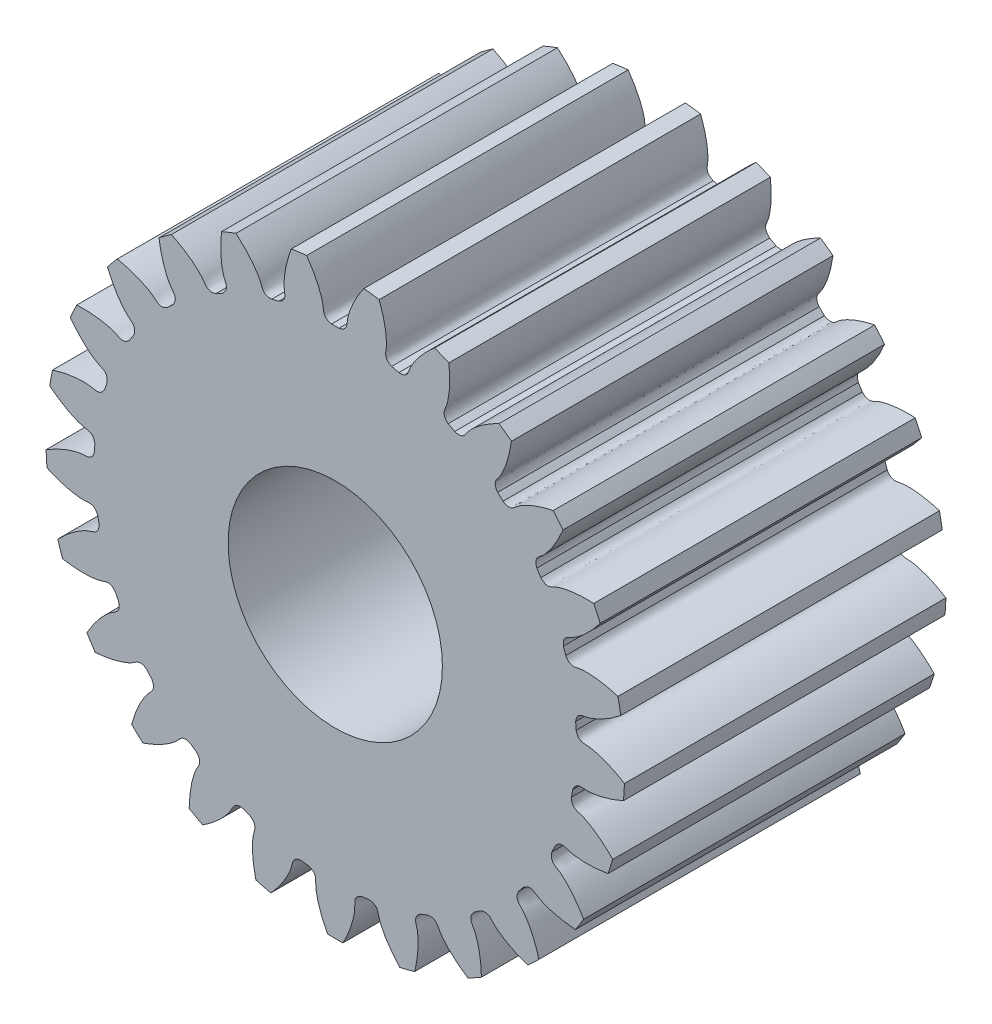
SolidWorks part; units mm, degrees
ref_plane "前视基准面" through (0, 0, 0) normal (0, 0, 1) x (1, 0, 0)
ref_plane "上视基准面" through (0, 0, 0) normal (0, 1, 0) x (1, 0, 0)
ref_plane "右视基准面" through (0, 0, 0) normal (1, 0, 0) x (0, 0, -1)
sketch "草图1" plane through (0, 0, 0) normal (0, 0, 1) x (1, 0, 0)
  circle A0 centre (0, 0) radius 2.7
extrude "凸台-拉伸1" add sketch "草图1" along normal blind 3
ref_axis "基准轴1" through (0, 0, 3) along (0, 0, -1)
sketch "草图2" plane through (0, 0, 0) normal (0, 0, 1) x (1, 0, 0)
  line L0 (0, 0) -> (0, 2.7) construction
  circle A0 centre (0, 0) radius 2.7 construction
  arc A1 (0.0344, 2.2497) -> (-0.0344, 2.2497) centre (0, 0) ccw
  arc A2 (0.6411, 3.063) -> (-0.6411, 3.063) centre (0, 0) ccw
  spline S0 degree 3 poles (0.0344, 2.2497) (0.1147, 2.267) (0.1071, 2.3155) (0.1148, 2.3636) (0.1159, 2.3696) (0.1173, 2.3765) (0.119, 2.3843) (0.1212, 2.393) (0.1237, 2.4025) (0.1266, 2.4129) (0.1301, 2.4242) (0.1341, 2.4362) (0.1386, 2.4491) (0.1437, 2.4627) (0.1494, 2.4771) (0.1558, 2.4923) (0.1629, 2.5082) (0.1706, 2.5248) (0.1792, 2.542) (0.1885, 2.56) (0.1986, 2.5785) (0.2095, 2.5977) (0.2213, 2.6175) (0.234, 2.6378) (0.2476, 2.6587) (0.2622, 2.68) (0.2777, 2.7019) (0.2942, 2.7241) (0.3117, 2.7468) (0.3303, 2.7699) (0.3499, 2.7933) (0.3706, 2.817) (0.3925, 2.8409) (0.4154, 2.8652) (0.4395, 2.8896) (0.4647, 2.9142) (0.4911, 2.9389) (0.5187, 2.9638) (0.5475, 2.9886) (0.588, 3.0223) (0.6195, 3.0468) (0.6411, 3.063) knots 0 0 0 0 0.130741 0.135745 0.141658 0.148481 0.156214 0.164857 0.174409 0.184871 0.196243 0.208524 0.221715 0.235816 0.250827 0.266748 0.283578 0.301318 0.319968 0.339527 0.359996 0.381375 0.403664 0.426862 0.450971 0.475988 0.501916 0.528753 0.556501 0.585157 0.614724 0.6452 0.676587 0.708882 0.742088 0.776203 0.811228 0.847163 0.884008 0.921762 1 1 1 1
  spline S1 degree 3 poles (-0.0344, 2.2497) (-0.1147, 2.267) (-0.1071, 2.3155) (-0.1148, 2.3636) (-0.1159, 2.3696) (-0.1173, 2.3765) (-0.119, 2.3843) (-0.1212, 2.393) (-0.1237, 2.4025) (-0.1266, 2.4129) (-0.1301, 2.4242) (-0.1341, 2.4362) (-0.1386, 2.4491) (-0.1437, 2.4627) (-0.1494, 2.4771) (-0.1558, 2.4923) (-0.1629, 2.5082) (-0.1706, 2.5248) (-0.1792, 2.542) (-0.1885, 2.56) (-0.1986, 2.5785) (-0.2095, 2.5977) (-0.2213, 2.6175) (-0.234, 2.6378) (-0.2476, 2.6587) (-0.2622, 2.68) (-0.2777, 2.7019) (-0.2942, 2.7241) (-0.3117, 2.7468) (-0.3303, 2.7699) (-0.3499, 2.7933) (-0.3706, 2.817) (-0.3925, 2.8409) (-0.4154, 2.8652) (-0.4395, 2.8896) (-0.4647, 2.9142) (-0.4911, 2.9389) (-0.5187, 2.9638) (-0.5475, 2.9886) (-0.588, 3.0223) (-0.6195, 3.0468) (-0.6411, 3.063) knots 0 0 0 0 0.130741 0.135745 0.141658 0.148481 0.156214 0.164857 0.174409 0.184871 0.196243 0.208524 0.221715 0.235816 0.250827 0.266748 0.283578 0.301318 0.319968 0.339527 0.359996 0.381375 0.403664 0.426862 0.450971 0.475988 0.501916 0.528753 0.556501 0.585157 0.614724 0.6452 0.676587 0.708882 0.742088 0.776203 0.811228 0.847163 0.884008 0.921762 1 1 1 1
extrude "切除-拉伸1" cut sketch "草图2" along normal through all
pattern_circular "阵列(圆周)1" count 25 every 14.4 about axis through (0, 0, 3) along (0, 0, -1) of "切除-拉伸1"
sketch "草图3" plane through (0, 0, 0) normal (0, 0, 1) x (1, 0, 0)
  circle A0 centre (0, 0) radius 2.5 construction
  dimension "Dn" = 5
sketch "草图4" plane through (0, 0, 0) normal (0, 0, 1) x (1, 0, 0)
  circle A0 centre (0, 0) radius 1
  dimension "D1" = 2
extrude "切除-拉伸2" cut sketch "草图4" along normal through all
